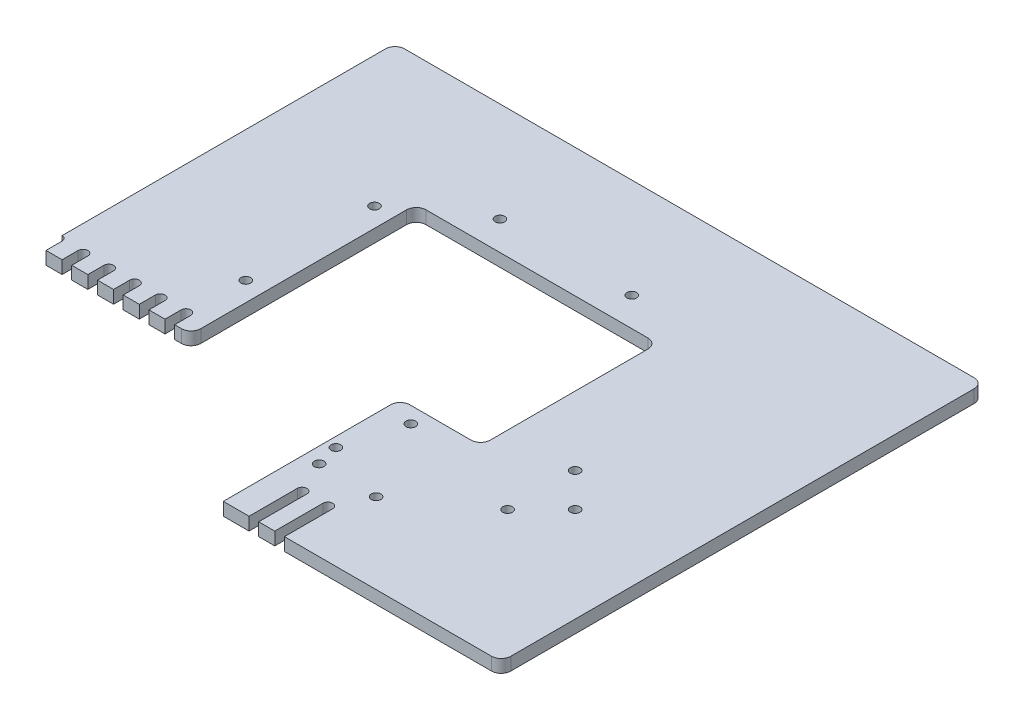
SolidWorks part; units mm, degrees
ref_plane "前视基准面" through (0, 0, 0) normal (0, 0, 1) x (1, 0, 0)
ref_plane "上视基准面" through (0, 0, 0) normal (0, 1, 0) x (1, 0, 0)
ref_plane "右视基准面" through (0, 0, 0) normal (1, 0, 0) x (0, 0, -1)
other "Configuration Table"
sketch "草图1" plane through (0, 0, 0) normal (0, 1, 0) x (1, 0, 0)
  line L5 (-51.0973, -171.2423) -> (-45.0973, -171.2423)
  line L6 (-45.0973, -171.2423) -> (-45.0973, -177.2423)
  line L7 (-45.0973, -177.2423) -> (-51.0973, -177.2423)
  line L8 (-80.0973, -171.2423) -> (-86.0973, -171.2423)
  line L12 (-86.0973, -171.2423) -> (-86.0973, -177.2423)
  line L13 (-86.0973, -177.2423) -> (-80.0973, -177.2423)
  line L14 (-80.0973, -113.2423) -> (-86.0973, -113.2423)
  line L37 (-88.3873, -92.2423) -> (105.4227, -92.2423) construction
  line L38 (105.4227, -92.2423) -> (105.4227, -192.2423) construction
  line L39 (105.4227, -192.2423) -> (-88.3873, -192.2423) construction
  line L40 (-88.3873, -192.2423) -> (-88.3873, -92.2423) construction
  line L42 (-105.0973, -197.2423) -> (122.1327, -197.2423)
  line L43 (122.1327, -197.2423) -> (122.1327, -87.2423)
  line L44 (122.1327, -87.2423) -> (-105.0973, -87.2423)
  line L46 (-105.0973, -87.2423) -> (-105.0973, -197.2423)
  line L48 (-80.0973, -87.2423) -> (-80.0973, -113.7423)
  line L49 (-80.0973, -113.7423) -> (-51.0973, -113.7423)
  line L50 (-51.0973, -113.7423) -> (-51.0973, -87.2423)
  line L52 (-80.0973, -197.2423) -> (-80.0973, -170.7423)
  line L53 (-80.0973, -170.7423) -> (-51.0973, -170.7423)
  line L54 (-51.0973, -170.7423) -> (-51.0973, -197.2423)
  line L56 (97.1327, -87.2423) -> (97.1327, -113.7423)
  line L57 (97.1327, -113.7423) -> (68.1327, -113.7423)
  line L58 (68.1327, -113.7423) -> (68.1327, -87.2423)
  line L60 (68.1327, -197.2423) -> (68.1327, -170.7423)
  line L61 (68.1327, -170.7423) -> (97.1327, -170.7423)
  line L62 (97.1327, -170.7423) -> (97.1327, -197.2423)
  line L63 (-86.0973, -113.2423) -> (-86.0973, -107.2423)
  line L64 (-86.0973, -107.2423) -> (-80.0973, -107.2423)
  line L66 (-51.0973, -107.2423) -> (-45.0973, -107.2423)
  line L67 (-45.0973, -107.2423) -> (-45.0973, -113.2423)
  line L68 (-45.0973, -113.2423) -> (-51.0973, -113.2423)
  line L70 (-86.0973, -110.2423) -> (-80.0973, -110.2423) construction
  line L72 (-83.0973, -107.2423) -> (-83.0973, -113.2423) construction
  line L73 (-51.0973, -110.2423) -> (-45.0973, -110.2423) construction
  line L74 (-48.0973, -107.2423) -> (-48.0973, -113.2423) construction
  line L75 (-86.0973, -174.2423) -> (-80.0973, -174.2423) construction
  line L76 (-83.0973, -171.2423) -> (-83.0973, -177.2423) construction
  line L77 (-48.0973, -171.2423) -> (-48.0973, -177.2423) construction
  line L78 (-45.0973, -174.2423) -> (-51.0973, -174.2423) construction
  line L79 (68.1327, -171.2423) -> (62.1327, -171.2423)
  line L80 (62.1327, -171.2423) -> (62.1327, -177.2423)
  line L81 (62.1327, -177.2423) -> (68.1327, -177.2423)
  line L82 (68.1327, -107.2423) -> (62.1327, -107.2423)
  line L83 (62.1327, -107.2423) -> (62.1327, -113.2423)
  line L84 (62.1327, -113.2423) -> (68.1327, -113.2423)
  line L85 (97.1327, -107.2423) -> (103.1327, -107.2423)
  line L86 (103.1327, -107.2423) -> (103.1327, -113.2423)
  line L87 (103.1327, -113.2423) -> (97.1327, -113.2423)
  line L88 (97.1327, -171.2423) -> (103.1327, -171.2423)
  line L89 (103.1327, -171.2423) -> (103.1327, -177.2423)
  line L90 (103.1327, -177.2423) -> (97.1327, -177.2423)
  line L91 (65.1327, -107.2423) -> (65.1327, -113.2423) construction
  line L92 (62.1327, -110.2423) -> (68.3912, -110.2423) construction
  line L93 (97.1327, -110.2423) -> (103.1327, -110.2423) construction
  line L94 (100.1327, -107.2423) -> (100.1327, -113.2423) construction
  line L95 (62.1327, -174.2423) -> (68.3912, -174.2423) construction
  line L96 (65.1327, -171.2423) -> (65.1327, -177.2423) construction
  line L97 (97.1327, -174.2423) -> (103.1327, -174.2423) construction
  line L98 (100.1327, -171.2423) -> (100.1327, -177.2423) construction
  line L99 (-105.0973, -142.2423) -> (122.1327, -142.2423) construction
  line L100 (8.5177, -87.2423) -> (8.5177, -197.2423) construction
  line L101 (8.5177, -97.2423) -> (8.5177, -137.2423) construction
  line L104 (10.0177, -97.2423) -> (10.0177, -137.2423)
  line L107 (7.0177, -97.2423) -> (7.0177, -137.2423)
  line L110 (8.5177, -147.2423) -> (8.5177, -187.2423) construction
  line L113 (10.0177, -147.2423) -> (10.0177, -187.2423)
  line L114 (7.0177, -147.2423) -> (7.0177, -187.2423)
  line L115 (16.5177, -97.2423) -> (16.5177, -137.2423) construction
  line L116 (18.0177, -97.2423) -> (18.0177, -137.2423)
  line L117 (15.0177, -97.2423) -> (15.0177, -137.2423)
  line L118 (16.5177, -147.2423) -> (16.5177, -187.2423) construction
  line L119 (18.0177, -147.2423) -> (18.0177, -187.2423)
  line L120 (15.0177, -147.2423) -> (15.0177, -187.2423)
  line L121 (24.5177, -97.2423) -> (24.5177, -137.2423) construction
  line L122 (26.0177, -97.2423) -> (26.0177, -137.2423)
  line L123 (23.0177, -97.2423) -> (23.0177, -137.2423)
  line L124 (24.5177, -147.2423) -> (24.5177, -187.2423) construction
  line L125 (26.0177, -147.2423) -> (26.0177, -187.2423)
  line L126 (23.0177, -147.2423) -> (23.0177, -187.2423)
  line L127 (32.5177, -97.2423) -> (32.5177, -137.2423) construction
  line L128 (34.0177, -97.2423) -> (34.0177, -137.2423)
  line L129 (31.0177, -97.2423) -> (31.0177, -137.2423)
  line L130 (40.5177, -97.2423) -> (40.5177, -137.2423) construction
  line L131 (42.0177, -97.2423) -> (42.0177, -137.2423)
  line L132 (39.0177, -97.2423) -> (39.0177, -137.2423)
  line L133 (32.5177, -147.2423) -> (32.5177, -187.2423) construction
  line L136 (40.5177, -147.2423) -> (40.5177, -187.2423) construction
  line L137 (42.0177, -147.2423) -> (42.0177, -187.2423)
  line L138 (39.0177, -147.2423) -> (39.0177, -187.2423)
  line L139 (34.0177, -147.2423) -> (34.0177, -187.2423)
  line L140 (31.0177, -147.2423) -> (31.0177, -187.2423)
  line L141 (0.5177, -97.2423) -> (0.5177, -137.2423) construction
  line L142 (2.0177, -97.2423) -> (2.0177, -137.2423)
  line L143 (-0.9823, -97.2423) -> (-0.9823, -137.2423)
  line L144 (-7.4823, -97.2423) -> (-7.4823, -137.2423) construction
  line L145 (-5.9823, -97.2423) -> (-5.9823, -137.2423)
  line L146 (-8.9823, -97.2423) -> (-8.9823, -137.2423)
  line L147 (-15.4823, -97.2423) -> (-15.4823, -137.2423) construction
  line L148 (-13.9823, -97.2423) -> (-13.9823, -137.2423)
  line L149 (-16.9823, -97.2423) -> (-16.9823, -137.2423)
  line L150 (-23.4823, -97.2423) -> (-23.4823, -137.2423) construction
  line L151 (-21.9823, -97.2423) -> (-21.9823, -137.2423)
  line L152 (-24.9823, -97.2423) -> (-24.9823, -137.2423)
  line L153 (0.5177, -147.2423) -> (0.5177, -187.2423) construction
  line L154 (2.0177, -147.2423) -> (2.0177, -187.2423)
  line L155 (-0.9823, -147.2423) -> (-0.9823, -187.2423)
  line L156 (-7.4823, -147.2423) -> (-7.4823, -187.2423) construction
  line L157 (-5.9823, -147.2423) -> (-5.9823, -187.2423)
  line L158 (-8.9823, -147.2423) -> (-8.9823, -187.2423)
  line L159 (-15.4823, -147.2423) -> (-15.4823, -187.2423) construction
  line L160 (-13.9823, -147.2423) -> (-13.9823, -187.2423)
  line L161 (-16.9823, -147.2423) -> (-16.9823, -187.2423)
  line L162 (-23.4823, -147.2423) -> (-23.4823, -187.2423) construction
  line L163 (-21.9823, -147.2423) -> (-21.9823, -187.2423)
  line L164 (-24.9823, -147.2423) -> (-24.9823, -187.2423)
  line L165 (-102.5973, -117.2423) -> (-102.5973, -167.2423) construction
  line L166 (-84.8973, -117.2423) -> (-84.8973, -167.2423) construction
  line L167 (119.6327, -117.2423) -> (119.6327, -167.2423) construction
  line L168 (119.6327, -167.2423) -> (101.9327, -167.2423) construction
  line L169 (101.9327, -167.2423) -> (101.9327, -117.2423) construction
  line L170 (101.9327, -117.2423) -> (119.6327, -117.2423) construction
  line L171 (-30.0973, -87.2423) -> (-30.0973, -102.2423)
  line L174 (-30.0973, -102.2423) -> (47.1327, -102.2423)
  line L177 (47.1327, -102.2423) -> (47.1327, -87.2423)
  line L180 (-30.0973, -197.2423) -> (-30.0973, -182.2423)
  line L183 (-57.5973, -147.2423) -> (-57.5973, -160.7423) construction
  line L186 (-56.0973, -147.2423) -> (-56.0973, -160.7423)
  line L189 (-59.0973, -147.2423) -> (-59.0973, -160.7423)
  line L190 (-97.5973, -127.2423) -> (-97.5973, -157.2423) construction
  line L191 (-96.0973, -127.2423) -> (-96.0973, -157.2423)
  line L192 (-99.0973, -127.2423) -> (-99.0973, -157.2423)
  line L193 (-89.5973, -127.2423) -> (-89.5973, -157.2423) construction
  line L194 (-88.0973, -127.2423) -> (-88.0973, -157.2423)
  line L195 (-91.0973, -127.2423) -> (-91.0973, -157.2423)
  line L196 (-65.5973, -147.2423) -> (-65.5973, -160.7423) construction
  line L197 (-64.0973, -147.2423) -> (-64.0973, -160.7423)
  line L198 (-67.0973, -147.2423) -> (-67.0973, -160.7423)
  line L199 (-73.5973, -147.2423) -> (-73.5973, -160.7423) construction
  line L200 (-72.0973, -147.2423) -> (-72.0973, -160.7423)
  line L201 (-75.0973, -147.2423) -> (-75.0973, -160.7423)
  line L202 (-73.5973, -137.2423) -> (-73.5973, -123.7423) construction
  line L203 (-75.0973, -137.2423) -> (-75.0973, -123.7423)
  line L204 (-72.0973, -137.2423) -> (-72.0973, -123.7423)
  line L205 (-65.5973, -137.2423) -> (-65.5973, -123.7423) construction
  line L206 (-67.0973, -137.2423) -> (-67.0973, -123.7423)
  line L207 (-64.0973, -137.2423) -> (-64.0973, -123.7423)
  line L208 (-57.5973, -137.2423) -> (-57.5973, -123.7423) construction
  line L209 (-59.0973, -137.2423) -> (-59.0973, -123.7423)
  line L210 (-56.0973, -137.2423) -> (-56.0973, -123.7423)
  line L211 (114.6327, -127.2423) -> (114.6327, -157.2423) construction
  line L212 (116.1327, -127.2423) -> (116.1327, -157.2423)
  line L213 (113.1327, -127.2423) -> (113.1327, -157.2423)
  line L214 (106.6327, -127.2423) -> (106.6327, -157.2423) construction
  line L215 (108.1327, -127.2423) -> (108.1327, -157.2423)
  line L216 (105.1327, -127.2423) -> (105.1327, -157.2423)
  line L217 (83.8086, -123.7423) -> (83.8086, -137.2423) construction
  line L218 (85.3086, -123.7423) -> (85.3086, -137.2423)
  line L219 (82.3086, -123.7423) -> (82.3086, -137.2423)
  line L220 (83.8086, -147.2423) -> (83.8086, -160.7423) construction
  line L221 (85.3086, -147.2423) -> (85.3086, -160.7423)
  line L222 (82.3086, -147.2423) -> (82.3086, -160.7423)
  line L223 (75.8086, -123.7423) -> (75.8086, -137.2423) construction
  line L224 (77.3086, -123.7423) -> (77.3086, -137.2423)
  line L225 (74.3086, -123.7423) -> (74.3086, -137.2423)
  line L226 (75.8086, -147.2423) -> (75.8086, -160.7423) construction
  line L227 (77.3086, -147.2423) -> (77.3086, -160.7423)
  line L228 (74.3086, -147.2423) -> (74.3086, -160.7423)
  line L229 (91.8086, -123.7423) -> (91.8086, -137.2423) construction
  line L230 (93.3086, -123.7423) -> (93.3086, -137.2423)
  line L231 (90.3086, -123.7423) -> (90.3086, -137.2423)
  line L232 (91.8086, -147.2423) -> (91.8086, -160.7423) construction
  line L233 (93.3086, -147.2423) -> (93.3086, -160.7423)
  line L234 (90.3086, -147.2423) -> (90.3086, -160.7423)
  line L235 (-141.4823, -142.2423) -> (158.5177, -142.2423) construction
  line L236 (-141.4823, 7.7577) -> (158.5177, 7.7577)
  line L237 (-141.4823, 7.7577) -> (-141.4823, -292.2423)
  line L238 (-141.4823, -292.2423) -> (158.5177, -292.2423)
  line L239 (158.5177, 7.7577) -> (158.5177, -292.2423)
  line L240 (-105.0973, -87.2423) -> (-105.0973, -32.2423) construction
  line L241 (-105.0973, -32.2423) -> (-30.0973, -32.2423) construction
  line L242 (-30.0973, -32.2423) -> (-30.0973, -87.2423) construction
  line L243 (-105.0973, -197.2423) -> (-105.0973, -252.2423) construction
  line L244 (-105.0973, -252.2423) -> (-30.0973, -252.2423) construction
  line L245 (-30.0973, -252.2423) -> (-30.0973, -197.2423) construction
  line L246 (122.1327, -87.2423) -> (122.1327, -32.2423) construction
  line L247 (122.1327, -32.2423) -> (47.1327, -32.2423) construction
  line L248 (47.1327, -32.2423) -> (47.1327, -87.2423) construction
  line L249 (122.1327, -197.2423) -> (122.1327, -252.2423) construction
  line L250 (122.1327, -252.2423) -> (47.1327, -252.2423) construction
  line L251 (47.1327, -252.2423) -> (47.1327, -197.2423) construction
  line L252 (-105.0973, -87.2423) -> (-105.0973, -32.2423)
  line L253 (-105.0973, -32.2423) -> (-30.0973, -32.2423)
  line L254 (-30.0973, -32.2423) -> (-30.0973, -87.2423)
  line L255 (47.1327, -87.2423) -> (47.1327, -32.2423)
  line L256 (47.1327, -32.2423) -> (122.1327, -32.2423)
  line L257 (122.1327, -32.2423) -> (122.1327, -87.2423)
  line L258 (-105.0973, -197.2423) -> (-105.0973, -252.2423)
  line L259 (-105.0973, -252.2423) -> (-30.0973, -252.2423)
  line L260 (-30.0973, -252.2423) -> (-30.0973, -197.2423)
  line L261 (47.1327, -197.2423) -> (47.1327, -252.2423)
  line L262 (47.1327, -252.2423) -> (122.1327, -252.2423)
  line L263 (122.1327, -252.2423) -> (122.1327, -197.2423)
  line L264 (-80.0973, -113.7423) -> (-80.0973, -171.2423)
  line L265 (97.1327, -113.7423) -> (97.1327, -170.7423)
  line L266 (-30.0973, -182.2423) -> (47.1327, -182.2423)
  line L267 (47.1327, -182.2423) -> (47.1327, -197.2423)
  line L268 (-141.4823, -142.2423) -> (158.5177, -142.2423)
  line L269 (-116.4823, 7.7577) -> (-116.4823, -292.2423)
  line L270 (158.5177, 7.7577) -> (183.5177, 7.7577)
  line L271 (183.5177, 7.7577) -> (183.5177, -292.2423)
  line L272 (183.5177, -292.2423) -> (158.5177, -292.2423)
  line L273 (158.5177, -142.2423) -> (183.5177, -142.2423)
  line L274 (143.5177, -89.7423) -> (143.5177, -194.7423) construction
  line L275 (143.5177, -89.7423) -> (143.5177, -79.2423) construction
  line L276 (143.5177, -89.7423) -> (154.0177, -89.7423) construction
  line L277 (143.5177, -194.7423) -> (143.5177, -205.2423) construction
  line L278 (143.5177, -194.7423) -> (154.0177, -194.7423) construction
  line L279 (0.5177, 7.7577) -> (0.5177, -95.7423)
  circle A9 centre (-88.3873, -92.2423) radius 1.5
  circle A10 centre (105.4227, -92.2423) radius 1.5
  circle A11 centre (105.4227, -192.2423) radius 1.5
  circle A12 centre (-88.3873, -192.2423) radius 1.5
  circle A13 centre (-37.0973, -92.2423) radius 1.5
  circle A14 centre (-37.0973, -192.2423) radius 1.5
  circle A15 centre (54.1327, -192.2423) radius 1.5
  circle A16 centre (54.1327, -92.2423) radius 1.5
  circle A17 centre (-83.0973, -110.2423) radius 1.5
  circle A18 centre (-48.0973, -110.2423) radius 1.5
  circle A19 centre (-83.0973, -174.2423) radius 1.5
  circle A20 centre (-48.0973, -174.2423) radius 1.5
  circle A21 centre (65.1327, -110.2423) radius 1.5
  circle A22 centre (100.1327, -110.2423) radius 1.5
  circle A23 centre (65.2619, -174.2423) radius 1.5
  circle A24 centre (100.1327, -174.2423) radius 1.5
  arc A33 (10.0177, -97.2423) -> (7.0177, -97.2423) centre (8.5177, -97.2423) ccw
  arc A34 (7.0177, -137.2423) -> (10.0177, -137.2423) centre (8.5177, -137.2423) ccw
  arc A35 (10.0177, -147.2423) -> (7.0177, -147.2423) centre (8.5177, -147.2423) ccw
  arc A36 (7.0177, -187.2423) -> (10.0177, -187.2423) centre (8.5177, -187.2423) ccw
  arc A37 (18.0177, -97.2423) -> (15.0177, -97.2423) centre (16.5177, -97.2423) ccw
  arc A38 (15.0177, -137.2423) -> (18.0177, -137.2423) centre (16.5177, -137.2423) ccw
  arc A39 (18.0177, -147.2423) -> (15.0177, -147.2423) centre (16.5177, -147.2423) ccw
  arc A40 (15.0177, -187.2423) -> (18.0177, -187.2423) centre (16.5177, -187.2423) ccw
  arc A41 (26.0177, -97.2423) -> (23.0177, -97.2423) centre (24.5177, -97.2423) ccw
  arc A42 (23.0177, -137.2423) -> (26.0177, -137.2423) centre (24.5177, -137.2423) ccw
  arc A43 (26.0177, -147.2423) -> (23.0177, -147.2423) centre (24.5177, -147.2423) ccw
  arc A44 (23.0177, -187.2423) -> (26.0177, -187.2423) centre (24.5177, -187.2423) ccw
  arc A45 (34.0177, -97.2423) -> (31.0177, -97.2423) centre (32.5177, -97.2423) ccw
  arc A46 (31.0177, -137.2423) -> (34.0177, -137.2423) centre (32.5177, -137.2423) ccw
  arc A47 (42.0177, -97.2423) -> (39.0177, -97.2423) centre (40.5177, -97.2423) ccw
  arc A48 (39.0177, -137.2423) -> (42.0177, -137.2423) centre (40.5177, -137.2423) ccw
  arc A51 (42.0177, -147.2423) -> (39.0177, -147.2423) centre (40.5177, -147.2423) ccw
  arc A52 (39.0177, -187.2423) -> (42.0177, -187.2423) centre (40.5177, -187.2423) ccw
  arc A53 (34.0177, -147.2423) -> (31.0177, -147.2423) centre (32.5177, -147.2423) ccw
  arc A54 (31.0177, -187.2423) -> (34.0177, -187.2423) centre (32.5177, -187.2423) ccw
  arc A55 (2.0177, -97.2423) -> (-0.9823, -97.2423) centre (0.5177, -97.2423) ccw
  arc A56 (-0.9823, -137.2423) -> (2.0177, -137.2423) centre (0.5177, -137.2423) ccw
  arc A57 (-5.9823, -97.2423) -> (-8.9823, -97.2423) centre (-7.4823, -97.2423) ccw
  arc A58 (-8.9823, -137.2423) -> (-5.9823, -137.2423) centre (-7.4823, -137.2423) ccw
  arc A59 (-13.9823, -97.2423) -> (-16.9823, -97.2423) centre (-15.4823, -97.2423) ccw
  arc A60 (-16.9823, -137.2423) -> (-13.9823, -137.2423) centre (-15.4823, -137.2423) ccw
  arc A61 (-21.9823, -97.2423) -> (-24.9823, -97.2423) centre (-23.4823, -97.2423) ccw
  arc A62 (-24.9823, -137.2423) -> (-21.9823, -137.2423) centre (-23.4823, -137.2423) ccw
  arc A63 (2.0177, -147.2423) -> (-0.9823, -147.2423) centre (0.5177, -147.2423) ccw
  arc A64 (-0.9823, -187.2423) -> (2.0177, -187.2423) centre (0.5177, -187.2423) ccw
  arc A65 (-5.9823, -147.2423) -> (-8.9823, -147.2423) centre (-7.4823, -147.2423) ccw
  arc A66 (-8.9823, -187.2423) -> (-5.9823, -187.2423) centre (-7.4823, -187.2423) ccw
  arc A67 (-13.9823, -147.2423) -> (-16.9823, -147.2423) centre (-15.4823, -147.2423) ccw
  arc A68 (-16.9823, -187.2423) -> (-13.9823, -187.2423) centre (-15.4823, -187.2423) ccw
  arc A69 (-21.9823, -147.2423) -> (-24.9823, -147.2423) centre (-23.4823, -147.2423) ccw
  arc A70 (-24.9823, -187.2423) -> (-21.9823, -187.2423) centre (-23.4823, -187.2423) ccw
  circle A71 centre (-102.5973, -117.2423) radius 1.5
  circle A72 centre (-102.5973, -167.2423) radius 1.5
  circle A73 centre (-84.8973, -117.2423) radius 1.5
  circle A74 centre (-84.8973, -167.2423) radius 1.5
  circle A75 centre (119.6327, -117.2423) radius 1.5
  circle A76 centre (119.6327, -167.2423) radius 1.5
  circle A78 centre (101.9327, -117.2423) radius 1.5
  circle A79 centre (101.9327, -167.2423) radius 1.5
  arc A98 (-56.0973, -147.2423) -> (-59.0973, -147.2423) centre (-57.5973, -147.2423) ccw
  arc A99 (-59.0973, -160.7423) -> (-56.0973, -160.7423) centre (-57.5973, -160.7423) ccw
  arc A100 (-96.0973, -127.2423) -> (-99.0973, -127.2423) centre (-97.5973, -127.2423) ccw
  arc A101 (-99.0973, -157.2423) -> (-96.0973, -157.2423) centre (-97.5973, -157.2423) ccw
  arc A102 (-88.0973, -127.2423) -> (-91.0973, -127.2423) centre (-89.5973, -127.2423) ccw
  arc A103 (-91.0973, -157.2423) -> (-88.0973, -157.2423) centre (-89.5973, -157.2423) ccw
  arc A104 (-64.0973, -147.2423) -> (-67.0973, -147.2423) centre (-65.5973, -147.2423) ccw
  arc A105 (-67.0973, -160.7423) -> (-64.0973, -160.7423) centre (-65.5973, -160.7423) ccw
  arc A106 (-72.0973, -147.2423) -> (-75.0973, -147.2423) centre (-73.5973, -147.2423) ccw
  arc A107 (-75.0973, -160.7423) -> (-72.0973, -160.7423) centre (-73.5973, -160.7423) ccw
  arc A108 (-75.0973, -137.2423) -> (-72.0973, -137.2423) centre (-73.5973, -137.2423) ccw
  arc A109 (-72.0973, -123.7423) -> (-75.0973, -123.7423) centre (-73.5973, -123.7423) ccw
  arc A110 (-67.0973, -137.2423) -> (-64.0973, -137.2423) centre (-65.5973, -137.2423) ccw
  arc A111 (-64.0973, -123.7423) -> (-67.0973, -123.7423) centre (-65.5973, -123.7423) ccw
  arc A112 (-59.0973, -137.2423) -> (-56.0973, -137.2423) centre (-57.5973, -137.2423) ccw
  arc A113 (-56.0973, -123.7423) -> (-59.0973, -123.7423) centre (-57.5973, -123.7423) ccw
  arc A114 (116.1327, -127.2423) -> (113.1327, -127.2423) centre (114.6327, -127.2423) ccw
  arc A115 (113.1327, -157.2423) -> (116.1327, -157.2423) centre (114.6327, -157.2423) ccw
  arc A116 (108.1327, -127.2423) -> (105.1327, -127.2423) centre (106.6327, -127.2423) ccw
  arc A117 (105.1327, -157.2423) -> (108.1327, -157.2423) centre (106.6327, -157.2423) ccw
  arc A118 (85.3086, -123.7423) -> (82.3086, -123.7423) centre (83.8086, -123.7423) ccw
  arc A119 (82.3086, -137.2423) -> (85.3086, -137.2423) centre (83.8086, -137.2423) ccw
  arc A120 (85.3086, -147.2423) -> (82.3086, -147.2423) centre (83.8086, -147.2423) ccw
  arc A121 (82.3086, -160.7423) -> (85.3086, -160.7423) centre (83.8086, -160.7423) ccw
  arc A122 (77.3086, -123.7423) -> (74.3086, -123.7423) centre (75.8086, -123.7423) ccw
  arc A123 (74.3086, -137.2423) -> (77.3086, -137.2423) centre (75.8086, -137.2423) ccw
  arc A124 (77.3086, -147.2423) -> (74.3086, -147.2423) centre (75.8086, -147.2423) ccw
  arc A125 (74.3086, -160.7423) -> (77.3086, -160.7423) centre (75.8086, -160.7423) ccw
  arc A126 (93.3086, -123.7423) -> (90.3086, -123.7423) centre (91.8086, -123.7423) ccw
  arc A127 (90.3086, -137.2423) -> (93.3086, -137.2423) centre (91.8086, -137.2423) ccw
  arc A128 (93.3086, -147.2423) -> (90.3086, -147.2423) centre (91.8086, -147.2423) ccw
  arc A129 (90.3086, -160.7423) -> (93.3086, -160.7423) centre (91.8086, -160.7423) ccw
  circle A130 centre (-23.4823, -97.2423) radius 1.5
  circle A131 centre (40.5177, -97.2423) radius 1.5
  circle A132 centre (-7.4823, -97.2423) radius 1.5
  circle A133 centre (24.5177, -97.2423) radius 1.5
  circle A134 centre (-23.4823, -187.2423) radius 1.5
  circle A135 centre (-7.4823, -187.2423) radius 1.5
  circle A136 centre (24.5177, -187.2423) radius 1.5
  circle A137 centre (40.5177, -187.2423) radius 1.5
  circle A138 centre (143.5177, -89.7423) radius 10.5 construction
  circle A139 centre (143.5177, -194.7423) radius 10.5 construction
  circle A140 centre (143.5177, -205.2423) radius 1.5
  circle A141 centre (154.0177, -194.7423) radius 1.5
  circle A142 centre (143.5177, -184.2423) radius 1.5
  circle A143 centre (143.5177, -79.2423) radius 1.5
  circle A144 centre (154.0177, -89.7423) radius 1.5
  circle A145 centre (143.5177, -100.2423) radius 1.5
  circle A146 centre (-23.4823, -25.2423) radius 1.5
  circle A147 centre (-83.4823, -25.2423) radius 1.5
  circle A148 centre (105.1327, -23.2423) radius 1.5
  circle A149 centre (41.1327, -39.2423) radius 1.5
  circle A150 centre (64.1327, -23.2423) radius 1.5
  circle A151 centre (41.1327, -79.2423) radius 1.5
  point P13 (-45.0973, -110.2423)
  point P124 (8.5177, -117.2423)
  point P129 (8.5177, -167.2423)
  point P138 (16.5177, -117.2423)
  point P143 (16.5177, -167.2423)
  point P150 (24.5177, -117.2423)
  point P157 (24.5177, -167.2423)
  point P166 (32.5177, -117.2423)
  point P171 (40.5177, -117.2423)
  point P180 (32.5177, -167.2423)
  point P186 (40.5177, -167.2423)
  point P191 (0.5177, -117.2423)
  point P198 (-7.4823, -117.2423)
  point P205 (-15.4823, -117.2423)
  point P212 (-23.4823, -117.2423)
  point P221 (0.5177, -167.2423)
  point P226 (-7.4823, -167.2423)
  point P233 (-15.4823, -167.2423)
  point P240 (-23.4823, -167.2423)
  point P265 (-31.4823, -117.2423)
  point P270 (-31.4823, -167.2423)
  point P277 (48.5177, -117.2423)
  point P284 (48.5177, -167.2423)
  point P293 (-57.5973, -153.9923)
  point P300 (-97.5973, -142.2423)
  point P307 (-89.5973, -142.2423)
  point P314 (-65.5973, -153.9923)
  point P319 (-73.5973, -153.9923)
  point P326 (-73.5973, -130.4923)
  point P333 (-65.5973, -130.4923)
  point P340 (-57.5973, -130.4923)
  point P347 (114.6327, -142.2423)
  point P354 (106.6327, -142.2423)
  point P363 (83.8086, -130.4923)
  point P368 (83.8086, -153.9923)
  point P375 (75.8086, -130.4923)
  point P382 (75.8086, -153.9923)
  point P389 (91.8086, -130.4923)
  point P396 (91.8086, -153.9923)
  dimension "D23" = 3
  dimension "D24" = 3
  dimension "D27" = 5
  dimension "D30" = 3
  dimension "D35" = 3
  dimension "D11" = 3
  dimension "D13" = 3
  dimension "D16" = 6
  dimension "D36" = 3
  dimension "D38" = 3
  dimension "D39" = 3
  dimension "D51" = 3
  dimension "D54" = 3
  dimension "D56" = 3
  dimension "D58" = 3
  dimension "D12" = 3
  dimension "D14" = 3
  dimension "D20" = 3
  dimension "D21" = 3
  dimension "D22" = 3
  dimension "D80" = 3
  dimension "D81" = 3
  dimension "D84" = 3
  dimension "D85" = 3
  dimension "D88" = 3
  dimension "D89" = 3
  dimension "D90" = 3
  dimension "D91" = 3
  dimension "D153" = 3
  dimension "D154" = 3
  dimension "D155" = 3
  dimension "D156" = 3
  dimension "D157" = 3
  dimension "D158" = 3
  dimension "D159" = 3
  dimension "D160" = 3
  dimension "D162" = 3
  dimension "D163" = 3
  dimension "D164" = 3
  dimension "D165" = 3
  dimension "D166" = 3
  dimension "D167" = 3
  dimension "D168" = 21
  dimension "D169" = 21
  dimension "D173" = 3
  dimension "D174" = 3
  dimension "D176" = 3
  dimension "D179" = 3
  dimension "D181" = 3
  dimension "D183" = 3
  dimension "D1" = 20
  dimension "D2" = 6
  dimension "D6" = 6
  dimension "D7" = 6
  dimension "D8" = 20
  dimension "D9" = 6
  dimension "D10" = 6
  dimension "D15" = 6
  dimension "D17" = 6
  dimension "D18" = 6
  dimension "D19" = 6
  dimension "D25" = 5
  dimension "D26" = 3
  dimension "D28" = 10
  dimension "D29" = 10
  dimension "D31" = 193.81
  dimension "D32" = 3
  dimension "D33" = 3
  dimension "D34" = 3
  dimension "D37" = 8
  dimension "D40" = 110
  dimension "D41" = 5
  dimension "D42" = 5
  dimension "D43" = 16.71
  dimension "D44" = 16.71
  dimension "D45" = 25
  dimension "D46" = 29
  dimension "D47" = 26.5
  dimension "D48" = 26.5
  dimension "D49" = 29
  dimension "D50" = 25
  dimension "D52" = 14
  dimension "D53" = 8
  dimension "D55" = 14
  dimension "D57" = 14
  dimension "D59" = 14
  dimension "D60" = 3
  dimension "D61" = 3
  dimension "D62" = 3
  dimension "D63" = 3
  dimension "D64" = 8
  dimension "D65" = 8
  dimension "D66" = 3
  dimension "D67" = 3
  dimension "D68" = 3
  dimension "D69" = 3
  dimension "D70" = 8
  dimension "D71" = 8
  dimension "D72" = 8
  dimension "D73" = 8
  dimension "D74" = 3
  dimension "D75" = 3
  dimension "D76" = 3
  dimension "D77" = 3
  dimension "D78" = 25
  dimension "D79" = 25
  dimension "D82" = 2.5
  dimension "D83" = 17.7
  dimension "D86" = 17.7
  dimension "D87" = 2.5
  dimension "D92" = 25
  dimension "D93" = 25
  dimension "D94" = 10
  dimension "D95" = 5
  dimension "D96" = 15
  dimension "D97" = 15
  dimension "D98" = 14.5
  dimension "D99" = 25
  dimension "D100" = 3
  dimension "D101" = 3
  dimension "D102" = 25
  dimension "D103" = 52.5
  dimension "D104" = 7.5
  dimension "D105" = 15
  dimension "D106" = 15
  dimension "D107" = 3
  dimension "D108" = 8
  dimension "D109" = 3
  dimension "D110" = 3
  dimension "D111" = 3
  dimension "D112" = 3
  dimension "D113" = 3
  dimension "D114" = 10
  dimension "D115" = 5
  dimension "D116" = 8
  dimension "D117" = 8
  dimension "D118" = 8
  dimension "D119" = 3
  dimension "D120" = 3
  dimension "D121" = 7.5
  dimension "D122" = 8
  dimension "D123" = 15
  dimension "D124" = 15
  dimension "D125" = 15
  dimension "D126" = 15
  dimension "D127" = 3
  dimension "D128" = 3
  dimension "D129" = 3
  dimension "D130" = 3
  dimension "D131" = 3
  dimension "D132" = 3
  dimension "D133" = 5
  dimension "D134" = 10
  dimension "D135" = 5
  dimension "D136" = 10
  dimension "D137" = 8
  dimension "D138" = 8
  dimension "D139" = 300
  dimension "D140" = 300
  dimension "D141" = 227.23
  dimension "D142" = 36.385
  dimension "D143" = 36.385
  dimension "D144" = 95
  dimension "D145" = 55
  dimension "D146" = 75
  dimension "D147" = 75
  dimension "D148" = 55
  dimension "D149" = 75
  dimension "D150" = 55
  dimension "D151" = 75
  dimension "D152" = 55
  dimension "D161" = 52.5
  dimension "D170" = 40
  dimension "D171" = 72
  dimension "D172" = 60
  dimension "D175" = 78.385
  dimension "D177" = 31
  dimension "D178" = 47
  dimension "D180" = 142.385
  dimension "D182" = 119.385
  dimension "D184" = 87
  dimension "D185" = 6
extrude "凸台-拉伸3" add sketch "草图1" along normal blind 4 contours A61 L151 L174 L149 A59 L148 L146 A57 L145 L143 A55 L142 L107 A33 L104 L117 A37 L116 L123 A41 L122 L129 A45 L128 L132 A47 L131 L177 L44 L171 L152 | L237 L268 L46 L252 L253 L254 L44 L255 L256 L257 L43 L239 L236 | A116 L215 L268 L213 A114 L212 L43 L44 L56 L85 L86 L87 L265 L216 A78 A75 A10 | L87 L86 L85 L56 A22 region at (109.8444, 0, 113.4331) region at (97.2175, 0, 110.2423) region at (79.5177, 0, -5.5791) region at (24.068, 0, 93.991)
extrude "凸台-拉伸4" add sketch "草图1<8>" along normal blind 4 contours L239 L273 L271 L270 region at (171.0177, 0, 67.2423)
sketch "草图1<8>" plane through (0, 0, 0) normal (0, 1, 0) x (1, 0, 0) same geometry as "草图1"
fillet "圆角1" radius 3 8 edges at (47.1327, 2, 32.2423) (122.1327, 2, 32.2423) (122.1327, 2, 87.2423) (97.1327, 2, 87.2423) (47.1327, 2, 102.2423) (183.5177, 2, -7.7577) (0.5177, 2, -7.7577) (183.5177, 2, 142.2423)
